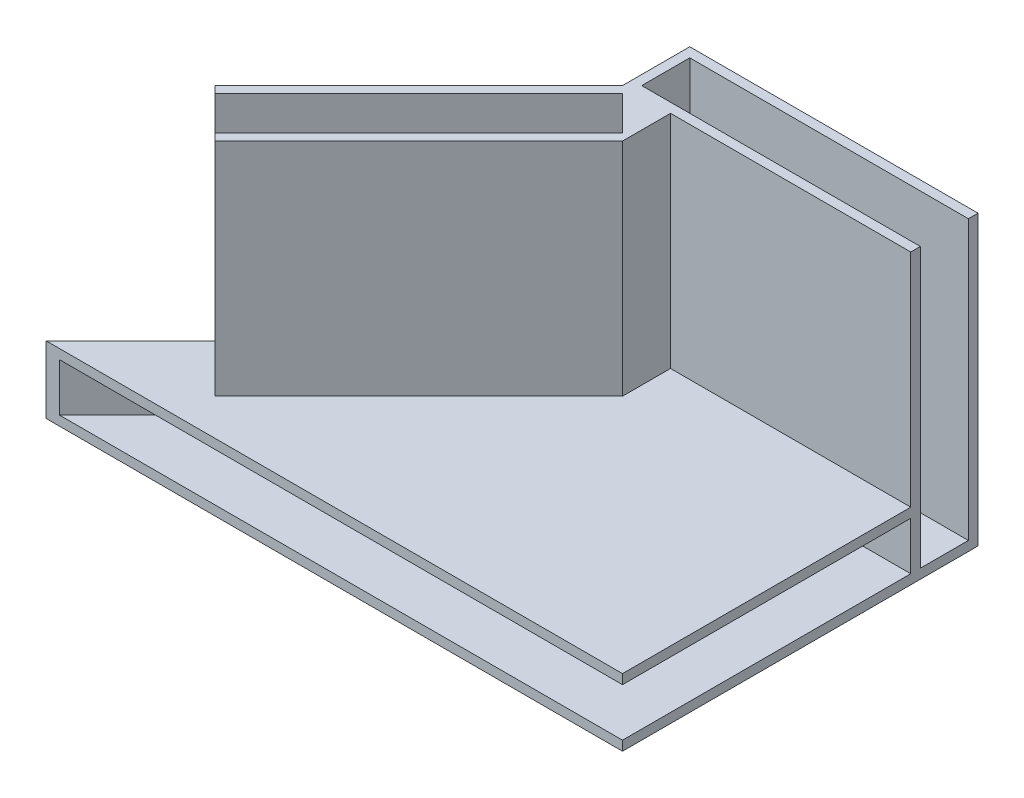
SolidWorks part; units mm, degrees
ref_plane "Front Plane" through (0, 0, 0) normal (0, 0, 1) x (1, 0, 0)
ref_plane "Top Plane" through (0, 0, 0) normal (0, 1, 0) x (1, 0, 0)
ref_plane "Right Plane" through (0, 0, 0) normal (1, 0, 0) x (0, 0, -1)
sketch "Sketch1" plane through (0, 0, 0) normal (0, 0, 1) x (1, 0, 0)
  line L1 (0, 0) -> (30, 0)
  line L2 (0, 0) -> (0, 30)
  line L3 (0, 30) -> (30, 30)
  line L4 (30, 0) -> (30, 30)
  dimension "D1" = 30
  dimension "D2" = 30
extrude "Boss-Extrude1" add sketch "Sketch1" along normal blind 7
shell "Shell1" thickness 1 removed face at (15, 0, 3.5) removed face at (30, 15, 3.5)
sketch "Sketch2" plane through (0, 0, 7) normal (0, 0, 1) x (1, 0, 0)
  line L0 (30, 0) -> (30, 30) construction
  line L1 (0, 30) -> (30, 30)
  line L2 (0, 30) -> (0, 23)
  line L3 (0, 23) -> (30, 23)
  line L4 (30, 30) -> (30, 23)
  dimension "D1" = 7
extrude "Boss-Extrude2" add sketch "Sketch2" along normal blind 30
sketch "Sketch3" plane through (0, 0, 0) normal (-1, 0, 0) x (0, 0, 1)
  line L1 (7, 23) -> (37, 23)
  line L2 (7, 23) -> (7, 30)
  line L3 (7, 30) -> (37, 30)
  line L4 (37, 23) -> (37, 30)
extrude "Boss-Extrude3" add sketch "Sketch3" along normal blind 30
sketch "Sketch4" plane through (0, 23, 0) normal (0, -1, 0) x (1, 0, 0)
  line L4 (-30, 37) -> (0, 7)
  line L5 (0, 7) -> (-30, 7)
  line L6 (-30, 7) -> (-30, 37)
sketch "Sketch5" plane through (0, 0, 7) normal (0, 0, 1) x (1, 0, 0)
  line L0 (0, 23) -> (30, 23) construction
  line L1 (0, 0) -> (5, 0)
  line L2 (0, 0) -> (0, 23)
  line L3 (0, 23) -> (5, 23)
  line L4 (5, 0) -> (5, 23)
  dimension "D1" = 5
extrude "Boss-Extrude4" add sketch "Sketch5" along normal blind 5
sketch "Sketch6" plane through (0, 0, 0) normal (0, -1, 0) x (1, 0, 0)
  line L3 (0, 12) -> (5, 12)
  line L4 (5, 7) -> (0, 7) construction
  line L5 (0, 12) -> (0, 0) construction
  line L6 (5, 12) -> (0, 7)
  line L7 (0, 7) -> (0, 12)
extrude "Cut-Extrude6" cut sketch "Sketch6" against normal blind 23
sketch "Sketch12" plane through (-3.5, 0, 3.5) normal (-0.7071, 0, 0.7071) x (0.7071, 0, 0.7071)
  line L4 (4.9497, 0) -> (12.0208, 0)
  line L5 (12.0208, 0) -> (12.0208, 23)
  line L6 (12.0208, 23) -> (4.9497, 23)
  line L7 (4.9497, 23) -> (4.9497, 0)
  line L8 (4.9497, 0) -> (12.0208, 0)
  line L9 (12.0208, 0) -> (12.0208, 23)
  line L10 (12.0208, 23) -> (4.9497, 23)
  line L11 (4.9497, 23) -> (4.9497, 0)
  dimension "D1" = 0
extrude "Boss-Extrude6" add sketch "Sketch12" along normal blind 30
sketch "Sketch13" plane through (0, 0, 0) normal (0, -1, 0) x (1, 0, 0)
  line L13 (0, 7) -> (5, 12) construction
  line L14 (-19.799, 28.2132) -> (0.7071, 7.7071)
  line L15 (-16.2132, 31.799) -> (4.2929, 11.2929)
  line L16 (4.2929, 11.2929) -> (0.7071, 7.7071)
  line L17 (-19.799, 28.2132) -> (-20.5061, 28.9203)
  line L18 (-21.2132, 28.2132) -> (-16.2132, 33.2132) construction
  line L19 (-16.2132, 31.799) -> (-16.9203, 32.5061)
  line L20 (-16.9203, 32.5061) -> (-20.5061, 28.9203)
extrude "Cut-Extrude7" cut sketch "Sketch13" against normal blind 22
extrude "Cut-Extrude8" cut sketch "Sketch4" against normal blind 22
shell "Shell2" thickness 1 removed face at (0, 26.5, 37)
sketch "Sketch16" plane through (0, 23, 0) normal (0, 1, 0) x (1, 0, 0)
  line L7 (1.4142, -7) -> (1, -7)
  line L8 (1, -7) -> (1, -7.4142)
  line L9 (1, -7.4142) -> (-19.799, -28.2132)
  line L10 (-19.799, -28.2132) -> (-16.2132, -31.799)
  line L11 (-16.2132, -31.799) -> (4, -11.5858)
  line L12 (4, -11.5858) -> (4, -9.5858)
  line L13 (4, -9.5858) -> (1.4142, -7)
  line L14 (1.4142, -7) -> (1, -7)
  line L15 (1, -7) -> (1, -7.4142)
  line L16 (1, -7.4142) -> (-19.799, -28.2132)
  line L17 (-19.799, -28.2132) -> (-16.2132, -31.799)
  line L18 (-16.2132, -31.799) -> (4, -11.5858)
  line L19 (4, -11.5858) -> (4, -9.5858)
  line L20 (4, -9.5858) -> (1.4142, -7)
  dimension "D1" = 0
extrude "Boss-Extrude7" add sketch "Sketch16" along normal blind 1
sketch "Sketch17" plane through (0, 30, 0) normal (0, 1, 0) x (1, 0, 0)
  line L5 (0, 0) -> (0, -7)
  line L6 (0, -7) -> (-30, -37)
  line L7 (-30, -37) -> (30, -37)
  line L8 (30, -37) -> (30, 0)
  line L9 (30, 0) -> (0, 0)
  line L10 (0, 0) -> (0, -7)
  line L11 (0, -7) -> (-30, -37)
  line L12 (-30, -37) -> (30, -37)
  line L13 (30, -37) -> (30, 0)
  line L14 (30, 0) -> (0, 0)
  dimension "D1" = 0
sketch "Sketch18" plane through (0, 1, 0) normal (0, 1, 0) x (1, 0, 0)
  line L3 (4, -9.5858) -> (4, -7)
  line L4 (4, -7) -> (1.4142, -7)
  line L5 (1.4142, -7) -> (4, -9.5858)
  line L6 (4, -9.5858) -> (4, -7)
  line L7 (4, -7) -> (1.4142, -7)
  line L8 (1.4142, -7) -> (4, -9.5858)
  dimension "D1" = 0
extrude "Boss-Extrude8" add sketch "Sketch18" along normal blind 23
sketch "Sketch19" plane through (30, 0, 0) normal (1, 0, 0) x (0, 0, -1)
  line L0 (-36, 29) -> (-37, 29)
  line L1 (-37, 29) -> (-37, 24)
  line L20 (-36, 24) -> (-37, 24)
  line L21 (-37, 23) -> (-37, 30) construction
  line L30 (-7, 29) -> (-36, 29)
  line L31 (-36, 29) -> (-36, 24)
  line L32 (-36, 24) -> (-7, 24)
  line L33 (-7, 24) -> (-7, 29)
  line L34 (-7, 29) -> (-36, 29)
  line L36 (-36, 24) -> (-7, 24)
  line L37 (-7, 24) -> (-7, 29)
  dimension "D1" = 1
extrude "Cut-Extrude10" cut sketch "Sketch19" against normal blind 1
mirror "Mirror4" about plane through (0, 0, 7) normal (0, 1, 0) of bodies 118
sketch "Sketch20" plane through (0, -30, 0) normal (0, -1, 0) x (1, 0, 0)
  line L5 (0, 7) -> (0, 0)
  line L6 (0, 0) -> (30, 0)
  line L7 (30, 0) -> (30, 37)
  line L8 (30, 37) -> (-30, 37)
  line L9 (-30, 37) -> (0, 7)
  line L10 (0, 7) -> (0, 0)
  line L11 (0, 0) -> (30, 0)
  line L12 (30, 0) -> (30, 37)
  line L13 (30, 37) -> (-30, 37)
  line L14 (-30, 37) -> (0, 7)
  dimension "D1" = 0
extrude "Cut-Extrude12" cut sketch "Sketch20" against normal blind 50 from offset 30 offset against normal yes
